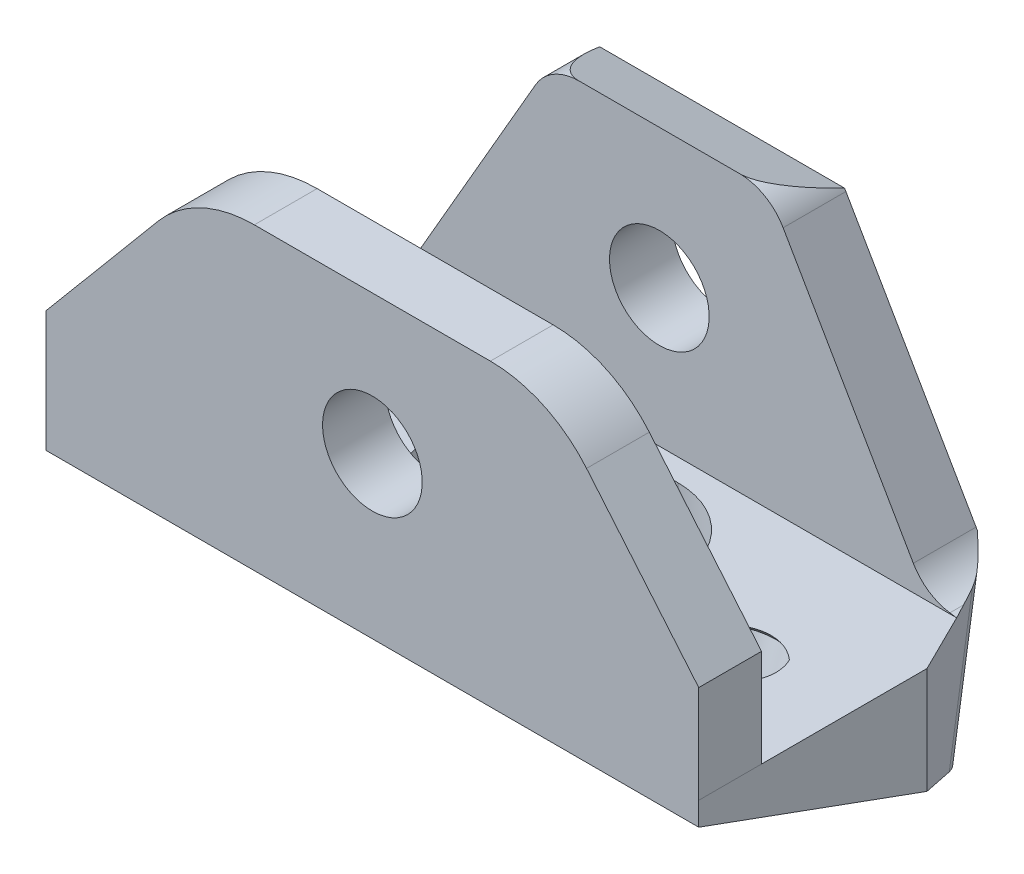
SolidWorks part; units mm, degrees
material "6061-T6 (SS)"
ref_plane "Front Plane" through (0, 0, 0) normal (0, 0, 1) x (1, 0, 0)
ref_plane "Top Plane" through (0, 0, 0) normal (0, 1, 0) x (1, 0, 0)
ref_plane "Right Plane" through (0, 0, 0) normal (1, 0, 0) x (0, 0, -1)
sketch "Sketch1" plane through (0, 0, 0) normal (0, 1, 0) x (1, 0, 0)
  line L0 (-26.9367, 35.3822) -> (26.9367, 35.3822)
  line L1 (-44.45, 0) -> (44.45, 0)
  line L2 (-26.9367, 35.3822) -> (-44.45, 0)
  line L3 (26.9367, 35.3822) -> (44.45, 0)
  point P2 (0, 35.3822)
  point P6 (0, 0)
  dimension "D1" = 53.8734
  dimension "D2" = 88.9
  dimension "D3" = 35.3822
extrude "Boss-Extrude1" add sketch "Sketch1" along normal blind 43.18
sketch "Sketch3" plane through (0, 43.18, 0) normal (0, 1, 0) x (1, 0, 0)
  line L0 (-30.0798, 29.0322) -> (30.0798, 29.0322)
  line L1 (-26.9367, 35.3822) -> (-44.45, 0) construction
  line L2 (44.45, 0) -> (26.9367, 35.3822) construction
  line L3 (-41.3069, 6.35) -> (41.3069, 6.35)
  line L4 (41.3069, 6.35) -> (30.0798, 29.0322)
  line L5 (-30.0798, 29.0322) -> (-41.3069, 6.35)
  line L6 (26.9367, 35.3822) -> (-26.9367, 35.3822) construction
  line L7 (-44.45, 0) -> (44.45, 0) construction
  dimension "D1" = 6.35
  dimension "D2" = 6.35
extrude "Cut-Extrude1" cut sketch "Sketch3" against normal blind 27.94
ref_plane "Plane2" through (0, 11.3716, -4.1389) normal (0, -0.9397, 0.342) x (-1, 0, 0)
sketch "Sketch6" plane through (0, 11.3716, -4.1389) normal (0, -0.9397, 0.342) x (-1, 0, 0)
  line L1 (-46.1149, -5.9462) -> (46.2877, -5.9462)
  line L2 (-46.1149, -5.9462) -> (-46.1149, 34.348)
  line L3 (-46.1149, 34.348) -> (46.2877, 34.348)
  line L4 (46.2877, -5.9462) -> (46.2877, 34.348)
extrude "Cut-Extrude3" cut sketch "Sketch6" along normal blind 25.4
hole_wizard "Tap Drill for M8x1.0 Tap1" positions "Sketch7" profile "Sketch8" hole size "M8x1.0" standard "ANSI Metric"
sketch "Sketch7" plane through (0, 11.3716, -4.1389) normal (0, -0.9397, 0.342) x (-1, 0, 0)
  line L0 (44.45, -4.4046) -> (-44.45, -4.4046) construction
  point P0 (22.225, 8.9889)
  point P2 (-22.225, 8.9889)
  dimension "D1" = 13.3934
  dimension "D2" = 44.45
  dimension "D3" = 22.225
sketch "Sketch8" plane through (-22.225, 8.2972, -12.5857) normal (1, 0, 0) x (0, -0.342, -0.9397)
  line L0 (0, 0) -> (0, 10.104)
  line L1 (0, 10.104) -> (3.5, 8.001)
  line L2 (3.5, 8.001) -> (3.5, 0)
  line L5 (3.5, 0) -> (0, 0)
  line L10 (0, 10.104) -> (-3.5, 8.001) construction
  line L11 (0, -6.35) -> (0, 107.95) construction
  dimension "Hole Dia." = 7
  dimension "Hole Depth" = 8.001
  dimension "Drill Angle" = 118
sketch "Sketch10" plane through (0, 15.24, -4.821) normal (0, -1, 0) x (1, 0, 0)
  line L0 (-4.1275, -13.6956) -> (4.1275, -13.6956) construction
  line L1 (-4.1275, -5.4406) -> (4.1275, -5.4406)
  line L2 (-4.1275, -21.9506) -> (4.1275, -21.9506)
  line L3 (-44.45, 4.821) -> (44.45, 4.821) construction
  arc A0 (-4.1275, -5.4406) -> (-4.1275, -21.9506) centre (-4.1275, -13.6956) ccw
  arc A1 (4.1275, -21.9506) -> (4.1275, -5.4406) centre (4.1275, -13.6956) ccw
  point P2 (0, -13.6956)
  dimension "D3" = 8.255
  dimension "D1" = 18.5166
  dimension "D2" = 8.255
extrude "Cut-Extrude4" cut sketch "Sketch10" along normal blind 12.7
sketch "Sketch11" plane through (0, 11.3716, -4.1389) normal (0, -0.9397, 0.342) x (1, 0, 0)
  line L0 (-26.9367, -33.2484) -> (26.9367, -33.2484)
  line L1 (26.9367, -33.2484) -> (29.4309, -27.886)
  line L2 (44.45, 4.4046) -> (26.9367, -33.2484) construction
  line L3 (29.4309, -27.886) -> (-29.4309, -27.886)
  line L4 (-26.9367, -33.2484) -> (-44.45, 4.4046) construction
  line L5 (-29.4309, -27.886) -> (-26.9367, -33.2484)
extrude "Cut-Extrude5" cut sketch "Sketch11" against normal blind 15.24
hole_wizard "3/8 Clearance Hole1" positions "Sketch12" profile "Sketch13" hole size "3/8" standard "ANSI Inch"
sketch "Sketch12" plane through (0, 0, -35.3822) normal (0, 0, -1) x (-1, 0, 0)
  line L0 (-30.0798, 15.24) -> (30.0798, 15.24) construction
  point P0 (0, 29.1084)
  dimension "D1" = 13.8684
sketch "Sketch13" plane through (0, 29.1084, -35.3822) normal (1, 0, 0) x (0, 1, 0)
  line L0 (0, 0) -> (0, 38.9705)
  line L1 (0, 38.9705) -> (5.0419, 35.941)
  line L2 (5.0419, 35.941) -> (5.0419, 0)
  line L5 (5.0419, 0) -> (0, 0)
  line L10 (0, 38.9705) -> (-5.0419, 35.941) construction
  line L11 (0, -6.35) -> (0, 107.95) construction
  dimension "Hole Dia." = 10.0838
  dimension "Hole Depth" = 35.941
  dimension "Drill Angle" = 118
sketch "Sketch14" plane through (0, 0, -35.3822) normal (0, 0, -1) x (-1, 0, 0)
  line L0 (-26.9367, 15.6787) -> (-11.0588, 43.18)
  line L1 (-26.9367, 43.18) -> (26.9367, 43.18) construction
  line L2 (-11.0588, 43.18) -> (-30.0798, 43.18)
  line L3 (-30.0798, 43.18) -> (-30.0798, 15.24)
  line L4 (-30.0798, 15.24) -> (-26.9367, 15.6787)
  line L5 (26.9367, 15.6787) -> (11.0588, 43.18)
  line L6 (11.0588, 43.18) -> (30.0798, 43.18)
  line L7 (30.0798, 43.18) -> (30.0798, 15.24)
  line L8 (30.0798, 15.24) -> (26.9367, 15.6787)
  dimension "D1" = 30
  dimension "D2" = 30
extrude "Cut-Extrude6" cut sketch "Sketch14" against normal blind 15.24
sketch "Sketch15" plane through (0, 0, -6.35) normal (0, 0, -1) x (-1, 0, 0)
  line L0 (-41.3069, 15.24) -> (-17.8625, 43.18)
  line L1 (41.3069, 43.18) -> (-41.3069, 43.18) construction
  line L2 (-17.8625, 43.18) -> (-44.45, 43.18)
  line L3 (-44.45, 43.18) -> (-44.45, 12.8781)
  line L4 (-44.45, 12.8781) -> (-41.3069, 15.24)
  line L5 (41.3069, 15.24) -> (17.8625, 43.18)
  line L6 (17.8625, 43.18) -> (44.45, 43.18)
  line L7 (44.45, 43.18) -> (44.45, 12.8781)
  line L8 (44.45, 12.8781) -> (41.3069, 15.24)
  dimension "D1" = 40
  dimension "D2" = 40
extrude "Cut-Extrude7" cut sketch "Sketch15" against normal blind 15.24
fillet "Fillet2" radius 12.7 4 edges at (-17.8625, 43.18, -3.175) (17.8625, 43.18, -3.175) (41.3069, 15.24, -3.175) (-41.3069, 15.24, -3.175)
fillet "Fillet3" radius 5.08 4 edges at (26.9367, 15.6787, -32.2072) (11.0588, 43.18, -32.2072) (-11.0588, 43.18, -32.2072) (-26.9367, 15.6787, -32.2072)
fillet "Fillet5" radius 5.08 2 edges at (28.1838, 8.7564, -32.8627) (-28.1838, 8.7564, -32.8627)
fillet "Fillet4" radius 12.7 1 edges at (0, 15.6787, -35.3822)
ref_plane "Plane3" through (-45.72, 0, 0) normal (1, 0, 0) x (0, 0, -1)
sketch "Sketch16" plane through (-45.72, 0, 0) normal (1, 0, 0) x (0, 0, -1)
  line L1 (-0.9089, 43.7467) -> (35.9662, 43.7467)
  line L2 (-0.9089, 43.7467) -> (-0.9089, 1.0237)
  line L3 (-0.9089, 1.0237) -> (35.9662, 1.0237)
  line L4 (35.9662, 43.7467) -> (35.9662, 1.0237)
extrude "Cut-Extrude8" cut sketch "Sketch16" along normal blind 12.7
ref_plane "Plane4" through (45.72, 0, 0) normal (-1, 0, 0) x (0, 0, 1)
sketch "Sketch18" plane through (45.72, 0, 0) normal (-1, 0, 0) x (0, 0, 1)
  line L1 (-36.1286, 44.1122) -> (0.6246, 44.1122)
  line L2 (-36.1286, 44.1122) -> (-36.1286, 1.2267)
  line L3 (-36.1286, 1.2267) -> (0.6246, 1.2267)
  line L4 (0.6246, 44.1122) -> (0.6246, 1.2267)
extrude "Cut-Extrude9" cut sketch "Sketch18" along normal blind 12.7
ref_plane "Plane5" through (0, 1.8341, 0) normal (0, 1, 0) x (1, 0, 0)
sketch "Sketch19" plane through (0, 0, 0) normal (1, 0, 0) x (0, 0, -1)
  line L0 (29.0322, 43.18) -> (35.3822, 40.8688)
  line L1 (35.3822, 17.9181) -> (35.3822, 40.64) construction
  line L2 (23.0921, 4.4732) -> (0, 12.8781) construction
  line L3 (29.0322, 43.18) -> (35.3822, 43.18)
  line L4 (35.3822, 43.18) -> (35.3822, 40.8688)
extrude "Cut-Extrude10" cut sketch "Sketch19" against normal through all both and the other way through all
sketch "Sketch20" plane through (33.02, 0, 0) normal (1, 0, 0) x (0, 0, -1)
  line L1 (0, 25.116) -> (6.35, 25.116)
  line L2 (0, 25.116) -> (0, 15.24)
  line L3 (0, 15.24) -> (6.35, 15.24)
  line L4 (6.35, 25.116) -> (6.35, 15.24)
split line "Split Line1"
sketch "Sketch21" plane through (-33.02, 0, 0) normal (-1, 0, 0) x (0, 0, 1)
  line L0 (-6.35, 15.24) -> (-23.0921, 15.24) construction
  line L1 (0, 25.116) -> (-6.35, 25.116)
  line L2 (0, 25.116) -> (0, 15.24)
  line L3 (0, 15.24) -> (-6.35, 15.24)
  line L4 (-6.35, 25.116) -> (-6.35, 15.24)
  line L5 (-6.35, 15.24) -> (-6.35, 25.116) construction
split line "Split Line2"
